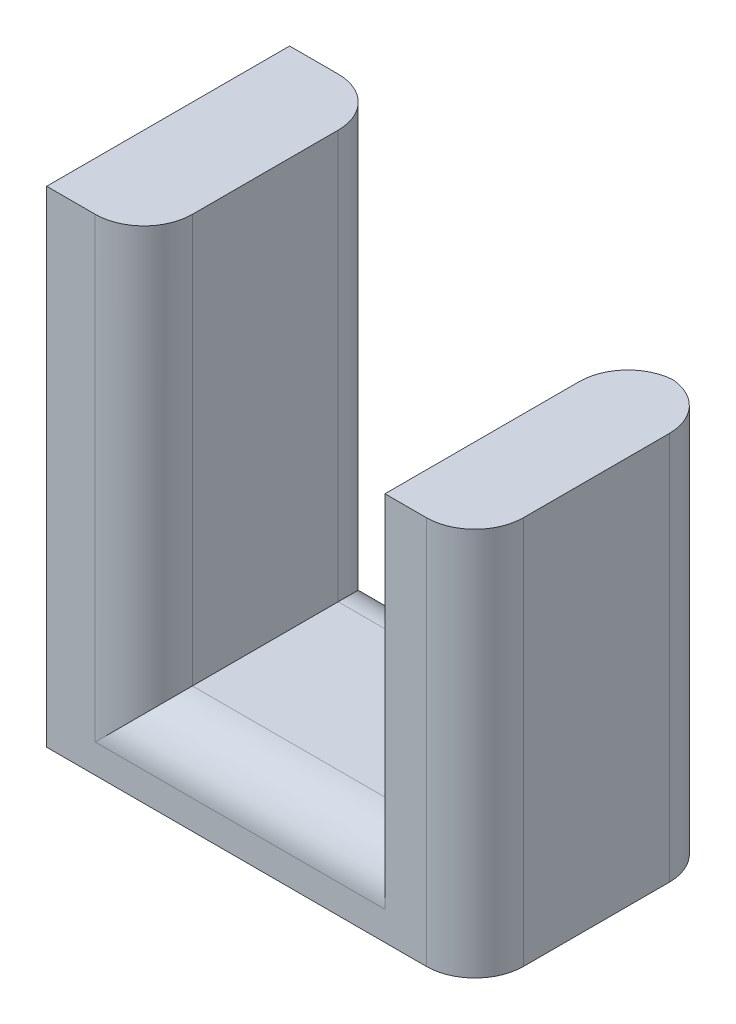
SolidWorks part; units mm, degrees
ref_plane "前基準面" through (0, 0, 0) normal (0, 0, 1) x (1, 0, 0)
ref_plane "上基準面" through (0, 0, 0) normal (0, 1, 0) x (1, 0, 0)
ref_plane "右基準面" through (0, 0, 0) normal (1, 0, 0) x (0, 0, -1)
sketch "草圖1" plane through (0, 0, 0) normal (0, 0, 1) x (1, 0, 0)
  line L0 (12.963, -21.0185) -> (47.037, -21.0185)
  line L1 (12.963, 28.9815) -> (2.963, 28.9815)
  line L3 (12.963, -21.0185) -> (2.963, -21.0185)
  line L4 (2.963, 28.9815) -> (2.963, -21.0185)
  line L13 (47.037, -21.0185) -> (47.037, 18.9815)
  line L14 (37.7778, 18.9815) -> (47.037, 18.9815)
  line L15 (37.7778, 18.9815) -> (37.7778, -13.0556)
  line L16 (37.7778, -13.0556) -> (12.963, -13.0556)
  line L17 (12.963, -13.0556) -> (12.963, 28.9815)
  dimension "D1" = 10
  dimension "D2" = 50
  dimension "D3" = 40
extrude "填料-伸長1" add sketch "草圖1" along normal blind 25
sketch "草圖2" plane through (2.963, 0, 0) normal (-1, 0, 0) x (0, 0, 1)
  circle A0 centre (12.5, 17.1397) radius 9.75
  dimension "D1" = 19.5
extrude "除料-伸長1" cut sketch "草圖2" against normal blind 5
fillet "圓角2" radius 5 7 edges at (47.037, -1.0185, 25) (47.037, -1.0185, 0) (37.7778, 2.963, 0) (12.963, 7.963, 25) (12.963, 7.963, 0) (25.3704, -13.0556, 25) (25.3704, -13.0556, 0)
